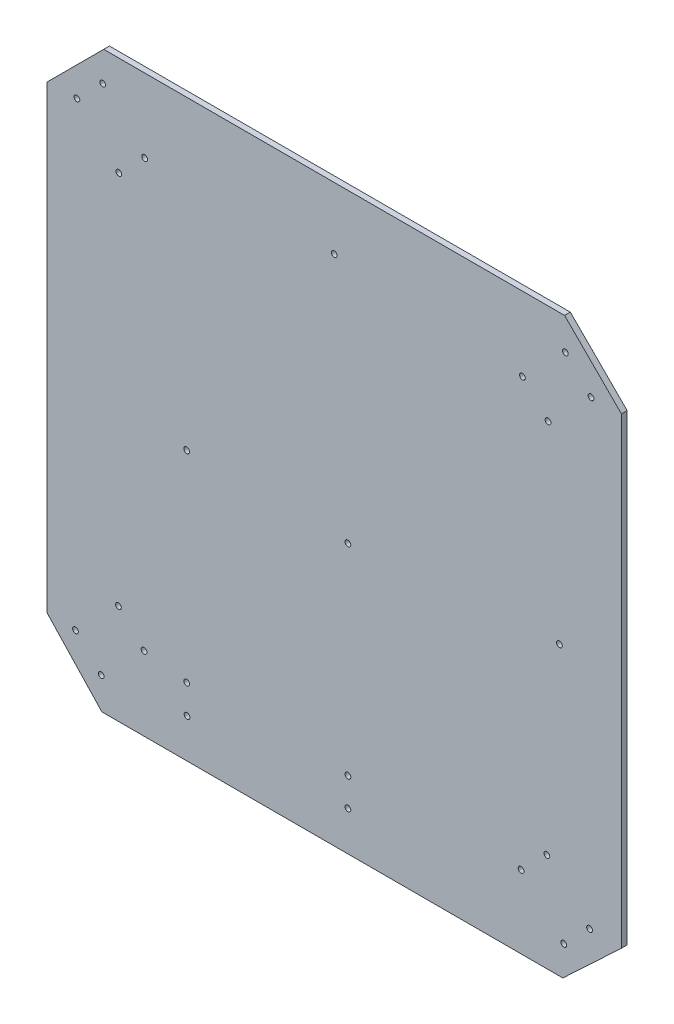
SolidWorks part; units mm, degrees
material "6061 Alloy"
ref_plane "Front Plane" through (0, 0, 0) normal (0, 0, 1) x (1, 0, 0)
ref_plane "Top Plane" through (0, 0, 0) normal (0, 1, 0) x (1, 0, 0)
ref_plane "Right Plane" through (0, 0, 0) normal (1, 0, 0) x (0, 0, -1)
sketch "Sketch2" plane through (0, 0, 0) normal (0, 0, 1) x (1, 0, 0)
  line L1 (-250, -250) -> (250, -250)
  line L2 (-250, -250) -> (-250, 250)
  line L3 (-250, 250) -> (250, 250)
  line L4 (250, -250) -> (250, 250)
  line L5 (-250, -250) -> (250, 250) construction
  line L6 (-250, 250) -> (250, -250) construction
  point P0 (0, 0)
  dimension "D1" = 500
  dimension "D2" = 500
extrude "Boss-Extrude1" add sketch "Sketch2" along normal blind 5
sketch "Sketch3" plane through (0, 0, 5) normal (0, 0, 1) x (1, 0, 0)
  line L0 (-250, 200.5025) -> (-200.5025, 250)
  line L1 (-250, 250) -> (-250, -250) construction
  line L2 (250, 250) -> (-250, 250) construction
  line L3 (-200.5025, 250) -> (-250, 250)
  line L4 (-250, 250) -> (-250, 200.5025)
  line L5 (200.5025, 250) -> (250, 200.5025)
  line L6 (250, -250) -> (250, 250) construction
  line L7 (250, 200.5025) -> (250, 250)
  line L8 (250, 250) -> (200.5025, 250)
  line L9 (-250, -198.9683) -> (-250, -250)
  line L10 (-250, -250) -> (-202.0859, -250)
  line L11 (-250, -250) -> (250, -250) construction
  line L12 (-202.0859, -250) -> (-250, -198.9683)
  line L13 (250, -202.0859) -> (250, -250)
  line L14 (250, -250) -> (198.9683, -250)
  line L15 (198.9683, -250) -> (250, -202.0859)
  line M13 (250, -250) -> (250, 250)
  line M14 (250, 250) -> (-250, 250)
  line M15 (-250, 250) -> (-250, -250)
  line M16 (-250, -250) -> (250, -250)
  dimension "D1" = 70
extrude "Cut-Extrude1" cut sketch "Sketch3" against normal blind 5 contours L0 M15 M14 | L5 M14 M13 | L15 M16 M13 | L12 M16 M15 region at (-233.5008, 233.5008, 5) region at (-234.0286, -232.9894, 5) region at (233.5008, 233.5008, 5) region at (232.9894, -234.0286, 5)
sketch "Sketch4" plane through (0, 0, 5) normal (0, 0, 1) x (1, 0, 0)
  line L0 (0, 244.9587) -> (-1.5588, -250) construction
  line L1 (-202.0859, -250) -> (198.9683, -250) construction
  line L2 (-250, 0.7671) -> (250, -0.7917) construction
  line L3 (-250, 200.5025) -> (-250, -198.9683) construction
  line L4 (250, -202.0859) -> (250, 200.5025) construction
  line L5 (-247.7019, 202.8006) -> (-202.8006, 247.7019)
  line L6 (-247.7019, 202.8006) -> (-176.9912, 132.0899)
  line L7 (-202.8006, 247.7019) -> (-132.0899, 176.9912)
  line L8 (-176.9912, 132.0899) -> (-132.0899, 176.9912)
  line L9 (-250, 200.5025) -> (-200.5025, 250) construction
  line L10 (-225.2513, 225.2513) -> (-154.5406, 154.5406) construction
  line L11 (-212.3466, 167.4453) -> (-167.4453, 212.3466) construction
  line L12 (211.8541, 166.1093) -> (167.2366, 211.2925) construction
  line L13 (225.1227, 223.8329) -> (153.968, 153.569) construction
  line L14 (176.2768, 130.9774) -> (131.6592, 176.1606)
  line L15 (202.8139, 246.4245) -> (131.6592, 176.1606)
  line L16 (247.4315, 201.2413) -> (176.2768, 130.9774)
  line L17 (247.4315, 201.2413) -> (202.8139, 246.4245)
  line L18 (210.8142, -167.4516) -> (165.9158, -212.3557) construction
  line L19 (246.1718, -202.8047) -> (201.2734, -247.7088)
  line L20 (201.2734, -247.7088) -> (130.5582, -177.0026)
  line L21 (223.7226, -225.2567) -> (153.0074, -154.5506) construction
  line L22 (246.1718, -202.8047) -> (175.4566, -132.0985)
  line L23 (175.4566, -132.0985) -> (130.5582, -177.0026)
  line L24 (-213.3866, -166.1426) -> (-168.7661, -211.3229) construction
  line L25 (-226.6514, -223.867) -> (-155.5012, -153.5986) construction
  line L26 (-177.8115, -131.0084) -> (-133.191, -176.1887)
  line L27 (-204.3412, -246.4572) -> (-133.191, -176.1887)
  line L28 (-248.9616, -201.2768) -> (-177.8115, -131.0084)
  line L29 (-248.9616, -201.2768) -> (-204.3412, -246.4572)
  circle A0 centre (-223.784, 201.3334) radius 2.5
  circle A1 centre (-201.3334, 223.784) radius 2.5
  circle A4 centre (186.1273, 163.0151) radius 2.5
  circle A5 centre (163.8185, 185.6067) radius 2.5
  circle A6 centre (201.196, 222.5163) radius 2.5
  circle A7 centre (223.5048, 199.9247) radius 2.5
  circle A8 centre (222.2538, -201.339) radius 2.5
  circle A9 centre (199.8046, -223.791) radius 2.5
  circle A10 centre (162.6579, -186.6491) radius 2.5
  circle A11 centre (185.1071, -164.197) radius 2.5
  circle A12 centre (-187.6599, -163.0467) radius 2.5
  circle A13 centre (-165.3497, -185.6369) radius 2.5
  circle A14 centre (-202.7249, -222.5489) radius 2.5
  circle A15 centre (-225.0351, -199.9587) radius 2.5
  circle A16 centre (-187.312, 163.5287) radius 2.5
  circle A17 centre (-164.8613, 185.9794) radius 2.5
  point P16 (-225.2513, 225.2513)
  point P17 (-225.2513, 225.2513)
  dimension "D3" = 5
  dimension "D1" = 100
  dimension "D2" = 63.5
  dimension "D4" = 31.75
  dimension "D5" = 31.75
  dimension "D6" = 52.53
  dimension "D7" = 52.53
  dimension "D8" = 17.95
extrude "Cut-Extrude4" cut sketch "Sketch4" against normal through all contours A0 | A1 | A16 | A6 | A7 | A5 | A9 | A8 | A12 | A13 | A15 | A14 | A17 | A4 | A11 | A10 region at (-223.784, 201.3334, 5) region at (-201.3334, 223.784, 5) region at (163.8185, 185.6067, 5) region at (201.196, 222.5163, 5) region at (223.5048, 199.9247, 5) region at (222.2538, -201.339, 5) region at (199.8046, -223.791, 5) region at (-187.6599, -163.0467, 5) region at (-165.3497, -185.6369, 5) region at (-202.7249, -222.5489, 5) region at (-225.0351, -199.9587, 5) region at (-187.312, 163.5287, 5)
sketch "Sketch6" plane through (0, 0, 5) normal (0, 0, 1) x (1, 0, 0)
  line L0 (-250, -216) -> (-128, -216) construction
  line L1 (-250, 200.5025) -> (-250, -198.9683) construction
  line L2 (-128, -216) -> (-128, -250) construction
  line L3 (-202.0859, -250) -> (198.9683, -250) construction
  circle A0 centre (-128, -216) radius 2.5
  circle A2 centre (-128.2846, -16) radius 2.5
  circle A3 centre (-128.2846, -191) radius 2.5
  circle A4 centre (12, -215.7153) radius 2.5
  circle A5 centre (12, -191) radius 2.5
  circle A6 centre (12, -16) radius 2.5
  dimension "D3" = 5
  dimension "D4" = 140
  dimension "D5" = 25
  dimension "D1" = 122
  dimension "D2" = 34
  dimension "D6" = 175
extrude "Cut-Extrude5" cut sketch "Sketch6" against normal through all contours A0 | A3 | A2 region at (-128, -216, 5) region at (-128.2846, -16, 5) region at (-128.2846, -191, 5)
extrude "Cut-Extrude6" cut sketch "Sketch6<3>" against normal through all contours A4 | A5 | A6 region at (12, -215.7153, 5) region at (12, -191, 5) region at (12, -16, 5)
sketch "Sketch6<3>" plane through (0, 0, 5) normal (0, 0, 1) x (1, 0, 0) same geometry as "Sketch6"
sketch "Sketch7" plane through (0, 0, 5) normal (0, 0, 1) x (1, 0, 0)
  line L0 (196, 250) -> (196, -250) construction
  line L3 (200.5025, 250) -> (-200.5025, 250) construction
  line L5 (-202.0859, -250) -> (198.9683, -250) construction
  line L6 (196, 0) -> (250, -0.7917) construction
  line L7 (250, -202.0859) -> (250, 200.5025) construction
  circle A0 centre (0, 196) radius 2.5
  circle A1 centre (196, 0) radius 2.5
  dimension "D1" = 54
extrude "Cut-Extrude7" cut sketch "Sketch7" against normal through all
